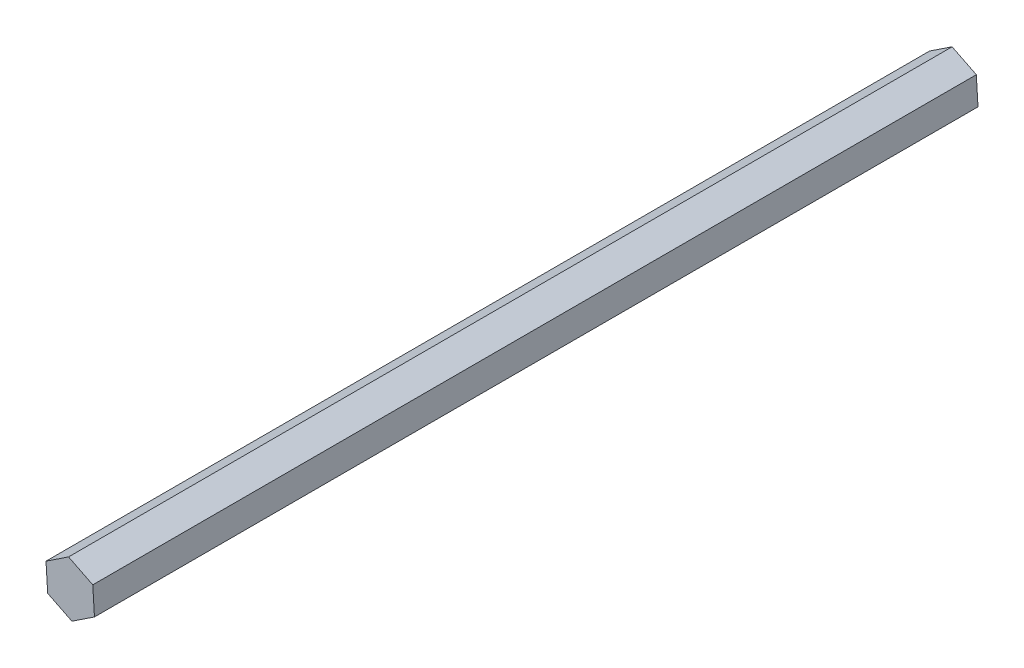
SolidWorks part; units mm, degrees
ref_plane "Front Plane" through (0, 0, 0) normal (0, 0, 1) x (1, 0, 0)
ref_plane "Top Plane" through (0, 0, 0) normal (0, 1, 0) x (1, 0, 0)
ref_plane "Right Plane" through (0, 0, 0) normal (1, 0, 0) x (0, 0, -1)
sketch "Sketch1" plane through (0, 0, 0) normal (0, 0, 1) x (1, 0, 0)
  line L1 (-0.4538, 7.336) -> (-6.58, 3.275)
  line L2 (-6.58, 3.275) -> (-6.1263, -4.061)
  line L3 (-6.1263, -4.061) -> (0.4538, -7.336)
  line L4 (0.4538, -7.336) -> (6.58, -3.275)
  line L5 (6.58, -3.275) -> (6.1263, 4.061)
  line L6 (6.1263, 4.061) -> (-0.4538, 7.336)
  circle A0 centre (0, 0) radius 6.3653 construction
  dimension "D1" = 7.35
extrude "Boss-Extrude1" add sketch "Sketch1" along normal blind 240
